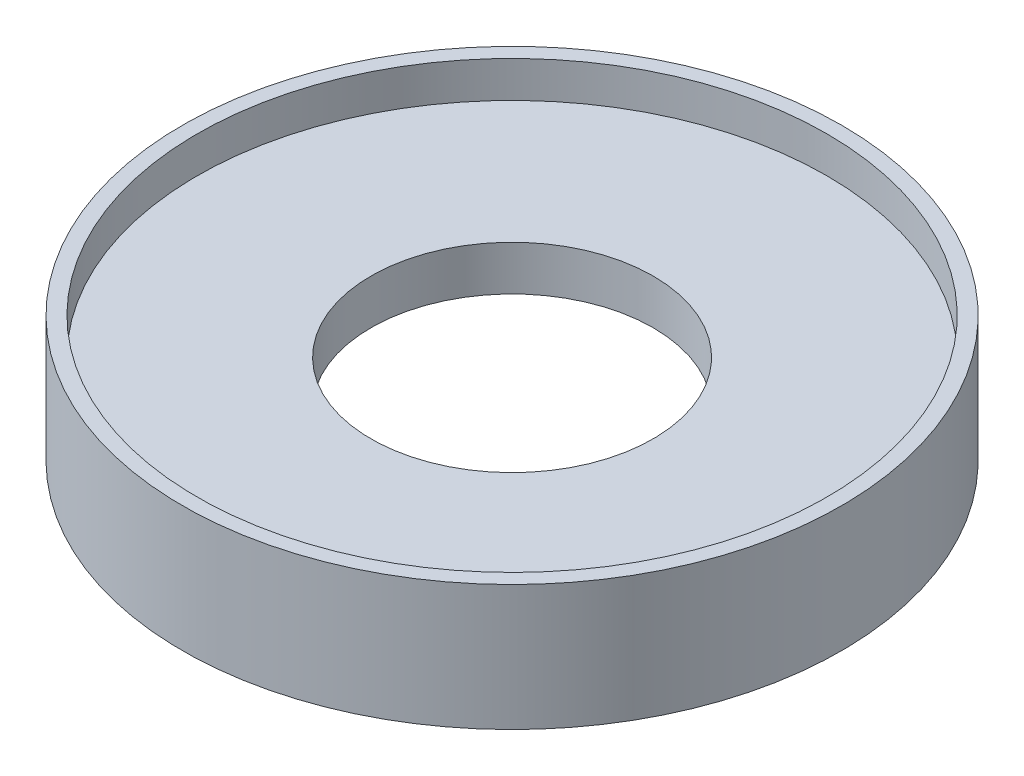
SolidWorks part; units mm, degrees
material "Al 6061-T6/T651"
ref_plane "Front Plane" through (0, 0, 0) normal (0, 0, 1) x (1, 0, 0)
ref_plane "Top Plane" through (0, 0, 0) normal (0, 1, 0) x (1, 0, 0)
ref_plane "Right Plane" through (0, 0, 0) normal (1, 0, 0) x (0, 0, -1)
sketch "Sketch1" plane through (0, 0, 0) normal (1, 0, 0) x (0, 0, -1)
  line L0 (19.05, 0) -> (42.5, 0)
  line L1 (42.5, 0) -> (42.5, -6)
  line L2 (42.5, -6) -> (44.5, -6)
  line L3 (44.5, -6) -> (44.5, 10.96)
  line L4 (44.5, 10.96) -> (42.5, 10.96)
  line L5 (42.5, 10.96) -> (42.5, 6.05)
  line L6 (42.5, 6.05) -> (19.05, 6.05)
  line L7 (19.05, 6.05) -> (19.05, 0)
  line L8 (0, 0) -> (0, 47.8452) construction
  dimension "D1" = 89
  dimension "D2" = 38.1
  dimension "D3" = 85
  dimension "D4" = 6
  dimension "D5" = 6.05
  dimension "D6" = 16.96
revolve "Revolve1" add sketch "Sketch1" angle 360 about L8
ref_point "Point1"
